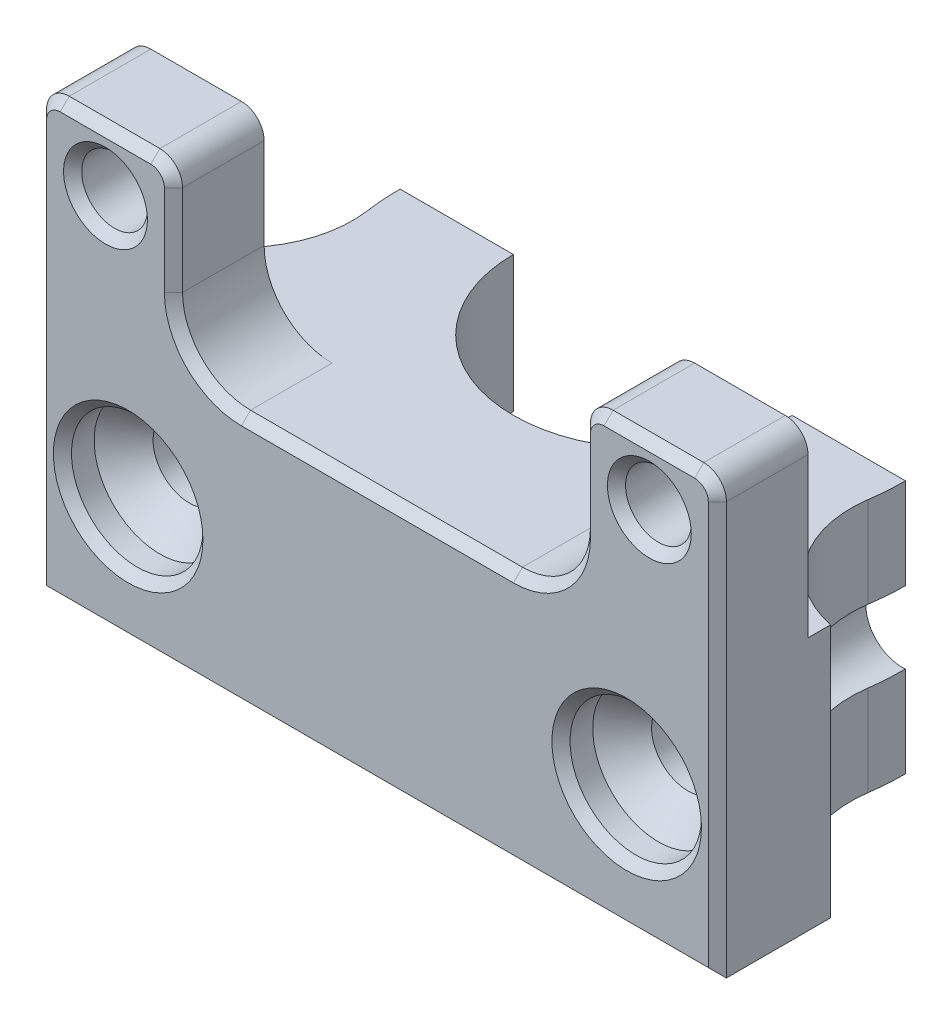
SolidWorks part; units mm, degrees
ref_plane "前视基准面" through (0, 0, 0) normal (0, 0, 1) x (1, 0, 0)
ref_plane "上视基准面" through (0, 0, 0) normal (0, 1, 0) x (1, 0, 0)
ref_plane "右视基准面" through (0, 0, 0) normal (1, 0, 0) x (0, 0, -1)
other "Configuration Table"
sketch "草图1" plane through (0, 0, 0) normal (0, 1, 0) x (1, 0, 0)
  line L0 (-11.15, 0) -> (-8.15, 0)
  line L1 (8.15, 0) -> (11.15, 0)
  arc A0 (-8.15, 0) -> (8.15, 0) centre (0, 0) ccw
  arc A1 (-11.15, 0) -> (11.15, 0) centre (0, 0) ccw
  circle A3 centre (0, 0) radius 11.15 construction
  circle A4 centre (0, 0) radius 8.15 construction
  point P4 (7.7939, 2.3828)
  point P7 (11.15, 0)
  dimension "D1" = 16.3
  dimension "D2" = 3
extrude "凸台-拉伸1" add sketch "草图1" along normal blind 5.2
sketch "草图2" plane through (0, 5.2, 0) normal (0, 1, 0) x (1, 0, 0)
  line L0 (-11.15, 0) -> (-6.15, 0)
  line L1 (6.15, 0) -> (11.15, 0)
  arc A0 (-11.15, 0) -> (11.15, 0) centre (0, 0) ccw
  arc A1 (-6.15, 0) -> (6.15, 0) centre (0, 0) ccw
  dimension "D1" = 12.3
extrude "凸台-拉伸2" add sketch "草图2" along normal blind 6
sketch "草图3" plane through (0, 11.2, 0) normal (0, 1, 0) x (1, 0, 0)
  line L0 (3.9115, -7.15) -> (15, -7.15)
  line L1 (-15, -7.15) -> (-3.9115, -7.15)
  line L2 (-15, -7.15) -> (-15, -11.15)
  line L3 (-15, -11.15) -> (15, -11.15)
  line L4 (15, -7.15) -> (15, -11.15)
  arc A0 (-11.15, 0) -> (11.15, 0) centre (0, 0) ccw construction
  arc A1 (-3.9115, -7.15) -> (3.9115, -7.15) centre (0, 0) ccw
  point P7 (0, -11.15)
  dimension "D1" = 11.15
  dimension "D2" = 30
  dimension "D3" = 0
  dimension "D4" = 4
extrude "凸台-拉伸3" add sketch "草图3" against normal up to surface (11.2 mm away) up to face at (0, 0, 4.825)
fillet "圆角1" radius 5 2 edges at (-8.5557, 5.6, 7.15) (8.5557, 5.6, 7.15)
sketch "草图4" plane through (0, 0, 11.15) normal (0, 0, 1) x (1, 0, 0)
  line L0 (-15, 0) -> (-15, 11.2) construction
  line L1 (15, 0) -> (15, 11.2) construction
  line L2 (-15, 11.2) -> (15, 11.2) construction
  circle A0 centre (-11, 5.6) radius 1.6
  circle A1 centre (11, 5.6) radius 1.6
  point P6 (-15, 5.6)
  point P9 (15, 5.6)
  point P12 (0, 11.2)
  dimension "D1" = 3.2
  dimension "D2" = 3.2
  dimension "D3" = 0
  dimension "D4" = 0
  dimension "D5" = 11
  dimension "D6" = 11
extrude "切除-拉伸1" cut sketch "草图4" against normal through all
sketch "草图7" plane through (0, 11.2, 0) normal (0, 1, 0) x (1, 0, 0)
  line L1 (-15, -11.15) -> (-9, -11.15)
  line L2 (-15, -11.15) -> (-15, -8.15)
  line L3 (-15, -8.15) -> (-9, -8.15)
  line L4 (-9, -11.15) -> (-9, -8.15)
  line L5 (15, -11.15) -> (9, -11.15)
  line L6 (15, -11.15) -> (15, -8.15)
  line L7 (15, -8.15) -> (9, -8.15)
  line L8 (9, -11.15) -> (9, -8.15)
  dimension "D1" = 3
  dimension "D2" = 3
  dimension "D3" = 6
  dimension "D4" = 6
extrude "凸台-拉伸5" add sketch "草图7" along normal blind 8
sketch "草图8" plane through (0, 0, 11.15) normal (0, 0, 1) x (1, 0, 0)
  line L0 (-15, 0) -> (-15, 19.2) construction
  circle A0 centre (-12, 16.6) radius 1.45
  circle A1 centre (12, 16.6) radius 1.45
  circle A2 centre (-11, 5.6) radius 1.6 construction
  circle A3 centre (11, 5.6) radius 1.6 construction
  dimension "D1" = 2.9
  dimension "D2" = 2.9
  dimension "D3" = 24
  dimension "D4" = 11
  dimension "D5" = 11
  dimension "D6" = 3
extrude "切除-拉伸3" cut sketch "草图8" against normal blind 8
sketch "草图9" plane through (0, 0, 11.15) normal (0, 0, 1) x (1, 0, 0)
  line L16 (-15, 19.2) -> (-15, 0)
  line L17 (-15, 0) -> (15, 0)
  line L18 (15, 0) -> (15, 19.2)
  line L19 (15, 19.2) -> (9, 19.2)
  line L20 (9, 19.2) -> (9, 11.2)
  line L21 (9, 11.2) -> (-9, 11.2)
  line L22 (-9, 11.2) -> (-9, 19.2)
  line L23 (-9, 19.2) -> (-15, 19.2)
  line L24 (-15, 19.2) -> (-15, 0)
  line L25 (-15, 0) -> (15, 0)
  line L26 (15, 0) -> (15, 19.2)
  line L27 (15, 19.2) -> (9, 19.2)
  line L28 (9, 19.2) -> (9, 11.2)
  line L29 (9, 11.2) -> (-9, 11.2)
  line L30 (-9, 11.2) -> (-9, 19.2)
  line L31 (-9, 19.2) -> (-15, 19.2)
  circle A0 centre (-12, 16.6) radius 1.45
  circle A1 centre (-11, 5.6) radius 1.6
  circle A2 centre (11, 5.6) radius 1.6
  circle A3 centre (12, 16.6) radius 1.45
  dimension "D1" = 0
extrude "凸台-拉伸6" add sketch "草图9" along normal blind 1
fillet "圆角2" radius 3 2 edges at (9, 11.2, 10.15) (-9, 11.2, 10.15)
fillet "圆角3" radius 1 4 edges at (15, 19.2, 10.15) (9, 19.2, 10.15) (-9, 19.2, 10.15) (-15, 19.2, 10.15)
sketch "草图10" plane through (0, 0, 12.15) normal (0, 0, 1) x (1, 0, 0)
  circle A0 centre (-11, 5.6) radius 2.9
  circle A1 centre (11, 5.6) radius 2.9
  dimension "D1" = 5.8
  dimension "D2" = 5.8
extrude "切除-拉伸4" cut sketch "草图10" against normal blind 2.7
chamfer "倒角2" distance 1.3 angle 45 2 edges at (-8.1, 5.6, 9.45) (13.9, 5.6, 9.45)
chamfer "倒角1" distance 0.4 angle 45 18 edges at (13.45, 16.6, 12.15) (0, 0, 12.15) (-15, 9.1, 12.15) (-14.7071, 18.9071, 12.15) (-12, 19.2, 12.15) (-9.2929, 18.9071, 12.15) (-9, 16.2, 12.15) (-8.1213, 12.0787, 12.15) (0, 11.2, 12.15) (8.1213, 12.0787, 12.15) (9, 16.2, 12.15) (9.2929, 18.9071, 12.15) (12, 19.2, 12.15) (14.7071, 18.9071, 12.15) (15, 9.1, 12.15) (-10.55, 16.6, 12.15) (13.9, 5.6, 12.15) (-8.1, 5.6, 12.15)
equation "\"D1@草图3\"=22.3/2"
equation "\"D5@草图8\"=\"D4@草图8\""
